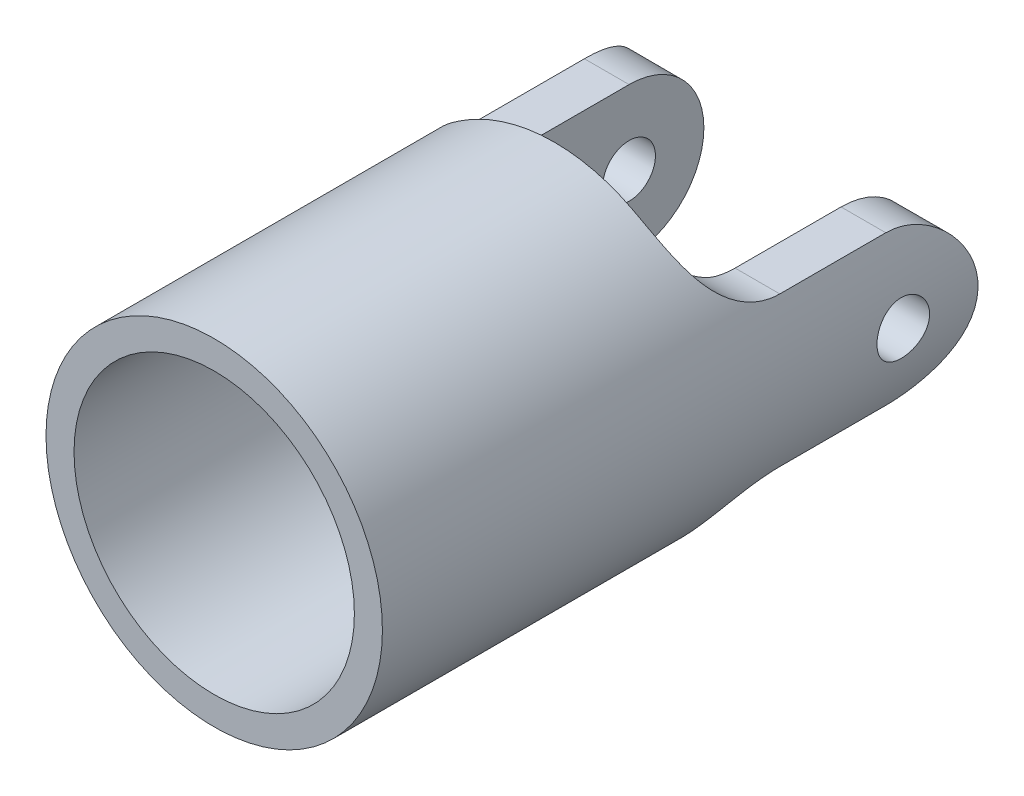
SolidWorks part; units mm, degrees
material "AISI 1020"
ref_plane "Front Plane" through (0, 0, 0) normal (0, 0, 1) x (1, 0, 0)
ref_plane "Top Plane" through (0, 0, 0) normal (0, 1, 0) x (1, 0, 0)
ref_plane "Right Plane" through (0, 0, 0) normal (1, 0, 0) x (0, 0, -1)
sketch "Sketch1" plane through (0, 0, 0) normal (1, 0, 0) x (0, 0, -1)
  line L0 (0, 0) -> (-34.925, 0) construction
  line L1 (-34.925, 9.525) -> (-34.925, 7.9375)
  line L2 (-34.925, 7.9375) -> (-15.925, 7.9375)
  line L3 (-15.925, 7.9375) -> (-15.925, 0)
  line L4 (-15.925, 0) -> (9.525, 0)
  line L5 (-34.925, 9.525) -> (9.525, 9.525)
  line L6 (9.525, 9.525) -> (9.525, 0)
  arc A0 (0, 9.525) -> (9.525, 0) centre (0, 0) cw construction
  dimension "D3" = 15.875
  dimension "D1" = 34.925
  dimension "D2" = 19
  dimension "D4" = 19.05
revolve "Revolve1" add sketch "Sketch1" angle 360 about L0
sketch "Sketch3" plane through (0, 0, 0) normal (1, 0, 0) x (0, 0, -1)
  line L0 (9.525, 9.525) -> (-34.925, 9.525) construction
  line L1 (9.525, 9.525) -> (-10.2333, 9.525)
  line L2 (-34.925, -9.525) -> (9.525, -9.525) construction
  line L3 (-10.2333, -9.525) -> (9.525, -9.525)
  line L4 (9.525, -9.525) -> (9.525, 9.525) construction
  line L5 (9.525, -9.525) -> (9.525, 9.525)
  line L6 (-10.2333, 8.4667) -> (-10.2333, 9.525)
  line L7 (-10.2333, -8.4667) -> (-10.2333, -9.525)
  line L8 (0, 4.2333) -> (-6, 4.2333)
  line L9 (0, -4.2333) -> (-6, -4.2333)
  arc A0 (0, -4.2333) -> (0, 4.2333) centre (0, 0) ccw
  arc A1 (-10.2333, 8.4667) -> (-6, 4.2333) centre (-6, 8.4667) ccw
  arc A2 (-10.2333, -8.4667) -> (-6, -4.2333) centre (-6, -8.4667) cw
  dimension "D1" = 4.2333
  dimension "D2" = 4.2333
  dimension "D3" = 6
extrude "Cut-Extrude1" cut sketch "Sketch3" against normal through all and the other way through all
sketch "Sketch4" plane through (0, 0, 0) normal (0, 1, 0) x (1, 0, 0)
  line L0 (-4.3636, -10.2333) -> (4.3636, -10.2333) construction
  line L1 (-2.825, -10.2333) -> (2.825, -10.2333)
  line L2 (0, 0) -> (0, -10.2333) construction
  line L4 (-6, -7.0583) -> (-6, 4.2333)
  line L5 (9.525, 4.2333) -> (-9.525, 4.2333) construction
  line L6 (6, 4.2333) -> (6, -7.0583)
  line L7 (6, 4.2333) -> (-6, 4.2333)
  arc A0 (-6, -7.0583) -> (-2.825, -10.2333) centre (-2.825, -7.0583) ccw
  arc A1 (6, -7.0583) -> (2.825, -10.2333) centre (2.825, -7.0583) cw
  point P14 (-6, -10.2333)
  point P17 (6, -10.2333)
  dimension "D2" = 3.175
  dimension "D1" = 12
extrude "Cut-Extrude2" cut sketch "Sketch4" against normal through all and the other way through all
sketch3d "3DSketch1"
  line L0 (0, 0, 0) -> (0, 0, 34.925)
  line L1 (0, 0, 34.925) -> (0, 0, 10.2333) construction
  line L2 (0, 0, 34.925) -> (0, 0, 15.925) construction
ref_axis "Axis1" through (39.0367, 0, 0) along (-1, 0, 0)
sketch "Sketch5" plane through (0, 0, 34.925) normal (0, 0, 1) x (1, 0, 0)
  line L1 (-11.8995, -11.4414) -> (11.8995, -11.4414)
  line L2 (-11.8995, -11.4414) -> (-11.8995, 11.4414)
  line L3 (-11.8995, 11.4414) -> (11.8995, 11.4414)
  line L4 (11.8995, -11.4414) -> (11.8995, 11.4414)
  line L5 (-11.8995, -11.4414) -> (11.8995, 11.4414) construction
  line L6 (-11.8995, 11.4414) -> (11.8995, -11.4414) construction
  point P0 (0, 0)
extrude "Cut-Extrude3" cut sketch "Sketch5" against normal blind 5.43
sketch "Sketch6" plane through (-6, 0, 0) normal (1, 0, 0) x (0, 0, -1)
  circle A0 centre (0, 0) radius 1.49
extrude "Cut-Extrude4" cut sketch "Sketch6" against normal blind 15.43 and the other way blind 25.43
